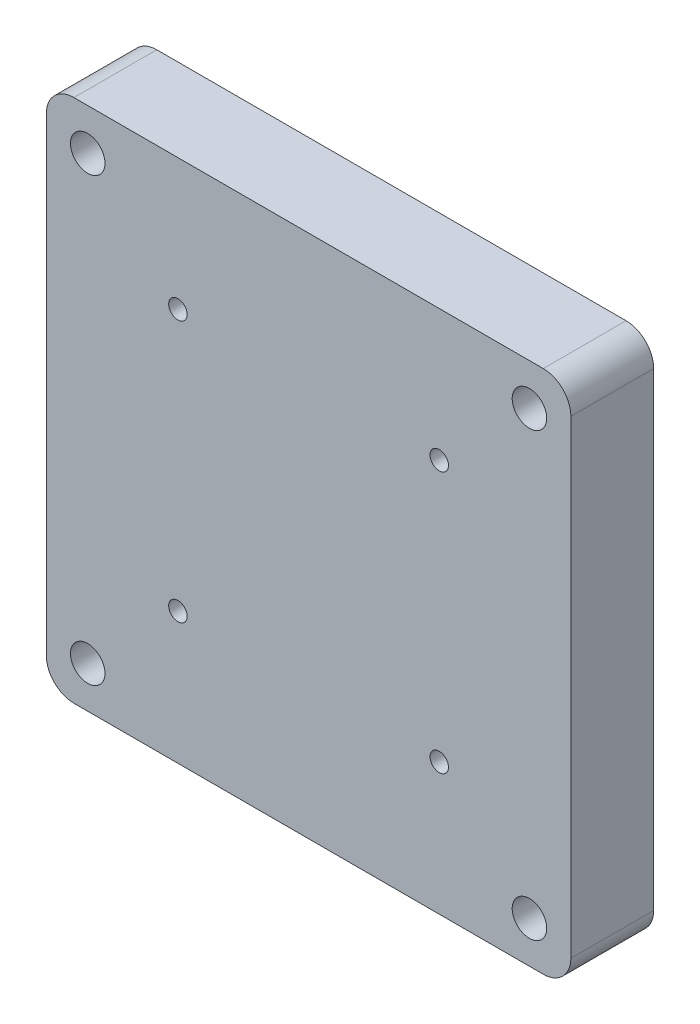
SolidWorks part; units mm, degrees
material "Nickel"
ref_plane "Front Plane" through (0, 0, 0) normal (0, 0, 1) x (1, 0, 0)
ref_plane "Top Plane" through (0, 0, 0) normal (0, 1, 0) x (1, 0, 0)
ref_plane "Right Plane" through (0, 0, 0) normal (1, 0, 0) x (0, 0, -1)
sketch "Sketch3" plane through (0, 0, 0) normal (0, 0, 1) x (1, 0, 0)
  line L0 (-120.65, 120.65) -> (120.65, 120.65)
  line L1 (-120.65, 120.65) -> (-120.65, -120.65)
  line L2 (-120.65, -120.65) -> (120.65, -120.65)
  line L3 (120.65, 120.65) -> (120.65, -120.65)
  line L12 (0, 120.65) -> (0, -120.65) construction
  line L14 (-60.1041, 60.2082) -> (60.1041, 60.2082) construction
  line L15 (-60.1041, 60.2082) -> (-60.1041, -60) construction
  line L16 (-60.1041, -60) -> (60.1041, -60) construction
  line L17 (60.1041, 60.2082) -> (60.1041, -60) construction
  line L18 (0, 60.2082) -> (0, -60) construction
  circle A1 centre (1.0535, 0.2618) radius 50 construction
  circle A13 centre (-60.1041, 60.2082) radius 4.25
  circle A14 centre (60.1041, 60.2082) radius 4.25
  circle A15 centre (60.1041, -60) radius 4.25
  circle A16 centre (-60.1041, -60) radius 4.25
  point P11 (0, 0)
  point P29 (1.0549, 0.2618)
  dimension "D3" = 100
  dimension "D7" = 8.5
  dimension "D1" = 241.3
  dimension "D2" = 241.3
  dimension "D4" = 170
  dimension "D6" = 60
extrude "Boss-Extrude1" add sketch "Sketch3" along normal blind 12.7
sketch "Sketch4" plane through (0, 0, 12.7) normal (0, 0, 1) x (1, 0, 0)
  line L0 (-101.6, -101.6) -> (-50.8, -101.6) construction
  line L1 (-101.6, -101.6) -> (-101.6, -50.8) construction
  line L2 (-101.6, -101.6) -> (101.6, 101.6) construction
  circle A16 centre (-101.6, -101.6) radius 7.9375
  circle A17 centre (-50.8, -101.6) radius 7.9375
  circle A18 centre (0, -101.6) radius 7.9375
  circle A19 centre (50.8, -101.6) radius 7.9375
  circle A20 centre (101.6, -101.6) radius 7.9375
  circle A21 centre (-50.8, -50.8) radius 7.9375
  circle A22 centre (0, -50.8) radius 7.9375
  circle A23 centre (50.8, -50.8) radius 7.9375
  circle A24 centre (101.6, -50.8) radius 7.9375
  circle A25 centre (-50.8, 0) radius 7.9375
  circle A27 centre (50.8, 0) radius 7.9375
  circle A28 centre (101.6, 0) radius 7.9375
  circle A29 centre (-50.8, 50.8) radius 7.9375
  circle A30 centre (0, 50.8) radius 7.9375
  circle A31 centre (50.8, 50.8) radius 7.9375
  circle A32 centre (101.6, 50.8) radius 7.9375
  circle A33 centre (-50.8, 101.6) radius 7.9375
  circle A34 centre (0, 101.6) radius 7.9375
  circle A35 centre (50.8, 101.6) radius 7.9375
  circle A36 centre (101.6, 101.6) radius 7.9375
  circle A37 centre (-101.6, -50.8) radius 7.9375
  circle A38 centre (-101.6, 0) radius 7.9375
  circle A39 centre (-101.6, 50.8) radius 7.9375
  circle A40 centre (-101.6, 101.6) radius 7.9375
  circle A41 centre (0, 0) radius 7.9375 [skipped]
  point P0 (0, 0)
  dimension "D1" = 15.875
  dimension "D4" = 5
  dimension "D5" = 5
  dimension "D2" = 50.8
  dimension "D3" = 50.8
extrude "Cut-Extrude1" cut sketch "Sketch4" against normal through all contours A16 | A20 | A36 | A40 region at (-101.6, -101.6, 12.7)
fillet "Fillet1" radius 12.7 4 edges at (-120.65, -120.65, 6.35) (-120.65, 120.65, 6.35) (120.65, 120.65, 6.35) (120.65, -120.65, 6.35)
sketch "Sketch5" plane through (0, 0, 0) normal (0, 0, -1) x (-1, 0, 0)
  line L4 (-107.95, -120.65) -> (107.95, -120.65)
  line L5 (120.65, -107.95) -> (120.65, 107.95)
  line L6 (107.95, 120.65) -> (-107.95, 120.65)
  line L7 (-120.65, 107.95) -> (-120.65, -107.95)
  line L8 (-107.95, -120.65) -> (107.95, -120.65)
  line L9 (120.65, -107.95) -> (120.65, 107.95)
  line L10 (107.95, 120.65) -> (-107.95, 120.65)
  line L11 (-120.65, 107.95) -> (-120.65, -107.95)
  circle A0 centre (101.6, 101.6) radius 7.9375 construction
  circle A1 centre (101.6, -101.6) radius 7.9375 construction
  circle A2 centre (-101.6, -101.6) radius 7.9375 construction
  circle A3 centre (-101.6, 101.6) radius 7.9375 construction
  arc A4 (107.95, -120.65) -> (120.65, -107.95) centre (107.95, -107.95) ccw
  arc A5 (120.65, 107.95) -> (107.95, 120.65) centre (107.95, 107.95) ccw
  arc A6 (-107.95, 120.65) -> (-120.65, 107.95) centre (-107.95, 107.95) ccw
  arc A7 (-120.65, -107.95) -> (-107.95, -120.65) centre (-107.95, -107.95) ccw
  arc A8 (107.95, -120.65) -> (120.65, -107.95) centre (107.95, -107.95) ccw
  arc A9 (120.65, 107.95) -> (107.95, 120.65) centre (107.95, 107.95) ccw
  arc A10 (-107.95, 120.65) -> (-120.65, 107.95) centre (-107.95, 107.95) ccw
  arc A11 (-120.65, -107.95) -> (-107.95, -120.65) centre (-107.95, -107.95) ccw
  circle A12 centre (101.6, 101.6) radius 7.9375
  circle A13 centre (101.6, -101.6) radius 7.9375
  circle A14 centre (-101.6, -101.6) radius 7.9375
  circle A15 centre (-101.6, 101.6) radius 7.9375
  circle A16 centre (-60.1041, 60.2082) radius 10.9995
  circle A17 centre (60.1041, 60.2082) radius 10.9995
  circle A18 centre (60.1041, -60) radius 10.9995
  circle A19 centre (-60.1041, -60) radius 10.9995
  dimension "D2" = 21.9989
  dimension "D1" = 0
extrude "Boss-Extrude2" add sketch "Sketch5" along normal blind 25.4
